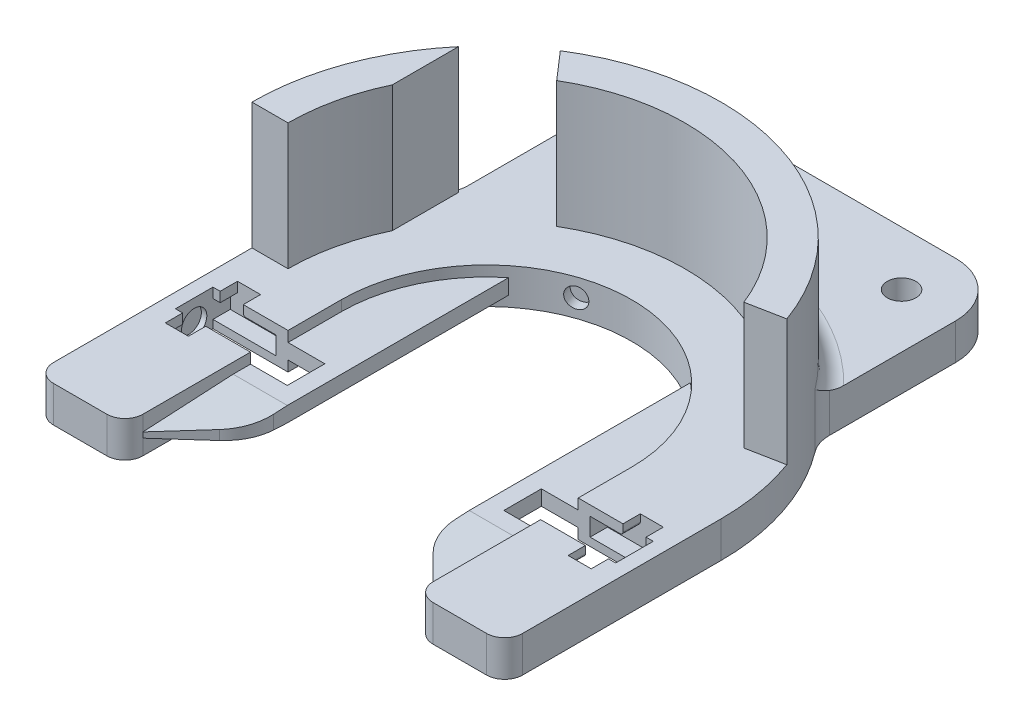
SolidWorks part; units mm, degrees
ref_plane "Front Plane" through (0, 0, 0) normal (0, 0, 1) x (1, 0, 0)
ref_plane "Top Plane" through (0, 0, 0) normal (0, 1, 0) x (1, 0, 0)
ref_plane "Right Plane" through (0, 0, 0) normal (1, 0, 0) x (0, 0, -1)
sketch "Sketch3" plane through (0, 0, 0) normal (0, 1, 0) x (1, 0, 0)
  line L0 (65, 0) -> (65, -55)
  line L1 (-65, 0) -> (65, 0) construction
  line L2 (60, -60) -> (45.2, -60)
  line L3 (40.2, -55) -> (40.2, 0)
  line L4 (25.2, -33.7868) -> (25.2, 31.3209)
  line L5 (29.5934, -44.3934) -> (40.2, -55)
  line L6 (54.9988, 0) -> (54.9988, -60)
  line L7 (0, -55) -> (0, 55) construction
  line L8 (-54.9988, 0) -> (-54.9988, -60)
  line L9 (-29.5934, -44.3934) -> (-40.2, -55)
  line L10 (-25.2, -33.7868) -> (-25.2, 31.3209)
  line L11 (-40.2, -55) -> (-40.2, 0)
  line L12 (-60, -60) -> (-45.2, -60)
  line L13 (-65, 0) -> (-65, -55)
  line L14 (-50, 80) -> (-50, 41.5331)
  line L15 (-35, 95) -> (35, 95)
  line L16 (50, 80) -> (50, 41.5331)
  arc A0 (65, 0) -> (-65, 0) centre (0, 0) ccw
  arc A1 (40.2, 0) -> (-40.2, 0) centre (0, 0) ccw
  arc A2 (60, -60) -> (65, -55) centre (60, -55) ccw
  arc A3 (45.2, -60) -> (40.2, -55) centre (45.2, -55) cw
  arc A4 (25.2, -33.7868) -> (29.5934, -44.3934) centre (40.2, -33.7868) ccw
  arc A5 (-54.9988, 0) -> (54.9988, 0) centre (0, 0) cw
  arc A6 (-25.2, -33.7868) -> (-29.5934, -44.3934) centre (-40.2, -33.7868) cw
  arc A7 (-45.2, -60) -> (-40.2, -55) centre (-45.2, -55) ccw
  arc A8 (-60, -60) -> (-65, -55) centre (-60, -55) cw
  arc A9 (50, 80) -> (35, 95) centre (35, 80) ccw
  arc A10 (-50, 80) -> (-35, 95) centre (-35, 80) cw
  circle A11 centre (-35, 80) radius 3.9688
  circle A12 centre (35, 80) radius 3.9688
  point P12 (65, -60)
  point P16 (40.2, -60)
  point P19 (25.2, -40)
  point P37 (-25.2, -40)
  point P38 (-40.2, -60)
  point P39 (-65, -60)
  point P45 (0, 65)
  point P52 (0, 95)
  dimension "130" = 130
  dimension "D4" = 80.4
  dimension "D8" = 5
  dimension "D9" = 15
  dimension "D10" = 54.9988
  dimension "D11" = 15
  dimension "D14" = 7.9375
  dimension "D2" = 60
  dimension "D3" = 24.8
  dimension "D5" = 15
  dimension "D6" = 5
  dimension "D7" = 15
  dimension "D12" = 30
  dimension "D13" = 100
extrude "Boss-Extrude1" add sketch "Sketch3" along normal mid plane 4.2 contours A1 L1 L10 | L1 L11 L9 A6 L10 | L4 L1 A1 | L1 L4 A4 L5 L3 region at (33.1426, 0, 23.8401) region at (31.3077, 0, -12.105) region at (-31.3077, 0, -12.105) region at (-33.1426, 0, 23.8401)
extrude "Boss-Extrude2" add sketch "Sketch3<3>" along normal mid plane 10 contours A5 L1 A1 | L1 L3 A3 L2 L6 | L1 L8 L12 A7 L11 region at (47.6376, 0, 29.8244) region at (47.5994, 0, -1.2298) region at (-47.6376, 0, 29.8244)
sketch "Sketch3<3>" plane through (0, 0, 0) normal (0, 1, 0) x (1, 0, 0) same geometry as "Sketch3"
extrude "Boss-Extrude3" add sketch "Sketch3<4>" against normal blind 5 and the other way blind 40 contours A0 L1 A5 | L1 L13 A8 L12 L8 | L1 L6 L2 A2 L0 region at (59.9643, 0, 29.7394) region at (59.9994, 0, -1.4534) region at (-59.9643, 0, 29.7394)
sketch "Sketch3<4>" plane through (0, 0, 0) normal (0, 1, 0) x (1, 0, 0) same geometry as "Sketch3"
sketch "Sketch4" plane through (0, 0, 0) normal (1, 0, 0) x (0, 0, -1)
  line L0 (-45, 5) -> (-60, 5)
  line L1 (-60, 5) -> (-60, 40)
  line L2 (-60, 40) -> (0, 40)
  line L3 (0, -5) -> (-55, -5) construction
  line L4 (0, 40) -> (-55, 40) construction
  line L5 (-60, 40) -> (-60, -5) construction
  arc A0 (-45, 5) -> (0, 40) centre (0, -6.4286) cw
  dimension "D2" = 15
  dimension "D1" = 10
extrude "Cut-Extrude1" cut sketch "Sketch4" against normal through all both and the other way through all
sketch "Sketch5" plane through (0, 40, 0) normal (0, 1, 0) x (1, 0, 0)
  line L0 (0, 0) -> (-42.6438, 49.0561) construction
  line L2 (-49.6832, 41.9115) -> (-43.0281, 34.2556) construction
  line L4 (-34.5891, 55.0327) -> (-27.9339, 47.3768)
  line L5 (0, 0) -> (0, 65) construction
  line L6 (-49.6832, 41.9115) -> (-49.6832, 23.5889)
  line L7 (0, 0) -> (63.8058, 12.4026) construction
  line L8 (51.1803, 20.1356) -> (61.1381, 22.0712)
  line L9 (54.9988, 0) -> (54.9988, -45)
  line L10 (54.9988, -45) -> (65, -45)
  line L11 (65, -45) -> (65, 0)
  line L12 (65, -45) -> (65, 0) construction
  line L13 (54.9988, 0) -> (54.9988, -45) construction
  line L14 (54.9988, -45) -> (65, -45) construction
  line L16 (-65, -45) -> (-54.9988, -45)
  line L17 (-65, -45) -> (-65, 0)
  line L18 (-65, 0) -> (-54.9988, 0)
  line L19 (-54.9988, -45) -> (-54.9988, 0)
  arc A0 (65, 0) -> (-65, 0) centre (0, 0) ccw construction
  arc A1 (-49.6832, 41.9115) -> (-34.5891, 55.0327) centre (0, 0) cw
  arc A2 (-43.0281, 34.2556) -> (-27.9339, 47.3768) centre (0, 0) cw
  arc A3 (54.9988, 0) -> (-54.9988, 0) centre (0, 0) ccw construction
  arc A4 (-49.6832, 23.5889) -> (-43.0281, 34.2556) centre (0, 0) cw
  arc A5 (54.9988, 0) -> (-54.9988, 0) centre (0, 0) ccw construction
  arc A6 (61.1381, 22.0712) -> (65, 0) centre (0, 0) cw
  arc A7 (51.1803, 20.1356) -> (54.9988, 0) centre (0, 0) cw
  dimension "D2" = 20
  dimension "D3" = 10
  dimension "D4" = 120
  dimension "D1" = 41
  dimension "D6" = 10
extrude "Cut-Extrude2" cut sketch "Sketch5" against normal blind 35
ref_axis "Axis1" through (0, 42.25, 0) along (0, -1, 0)
ref_plane "Plane1" through (0, 0, 0) normal (0.3256, 0, 0.9455) x (0, -1, 0)
sketch "Sketch6" plane through (0, 0, 0) normal (0.3256, 0, 0.9455) x (0, -1, 0)
  circle A0 centre (0, 0) radius 2.75
  dimension "D1" = 5.5
extrude "Cut-Extrude3" cut sketch "Sketch6" against normal blind 43
sketch "Sketch7" plane through (0, 5, 0) normal (0, 1, 0) x (1, 0, 0)
  line L0 (65, -55) -> (65, 0) construction
  line L1 (30, -14.8) -> (61, -14.8)
  line L2 (30, -14.8) -> (30, -25.2)
  line L3 (30, -25.2) -> (61, -25.2)
  line L4 (61, -14.8) -> (61, -25.2)
  line L6 (0, -24.75) -> (0, 24.75) construction
  line L7 (-61, -14.8) -> (-61, -25.2)
  line L8 (-30, -25.2) -> (-61, -25.2)
  line L9 (-30, -14.8) -> (-30, -25.2)
  line L10 (-30, -14.8) -> (-61, -14.8)
  line L11 (60, -60) -> (45.2, -60) construction
  point P7 (61, -20)
  dimension "D1" = 10.4
  dimension "D2" = 31
  dimension "D3" = 4
  dimension "D4" = 40
extrude "Cut-Extrude4" cut sketch "Sketch7" against normal through all
sketch "Sketch8" plane through (0, 0, 0) normal (0, 1, 0) x (1, 0, 0)
  line L0 (61, -25.2) -> (61, -14.8) construction
  line L1 (43.5, -10) -> (61, -10)
  line L2 (43.5, -10) -> (43.5, -30)
  line L3 (43.5, -30) -> (61, -30)
  line L4 (61, -10) -> (61, -30)
  line L6 (61, -14.8) -> (40.2, -14.8) construction
  line L7 (0, -24.75) -> (0, 24.75) construction
  line L8 (-61, -10) -> (-61, -30)
  line L9 (-43.5, -30) -> (-61, -30)
  line L10 (-43.5, -10) -> (-43.5, -30)
  line L11 (-43.5, -10) -> (-61, -10)
  dimension "D1" = 20
  dimension "D2" = 17.5
  dimension "D3" = 4.8
extrude "Cut-Extrude5" cut sketch "Sketch8" against normal blind 2.75 and the other way blind 2.25
sketch "Sketch12" plane through (61, 0, 0) normal (-1, 0, 0) x (0, 0, 1)
  line L0 (0, 0) -> (20, 0) construction
  circle A1 centre (20, -1) radius 3.5
  dimension "D1" = 20
  dimension "D2" = 7
  dimension "D3" = 1
extrude "Cut-Extrude7" cut sketch "Sketch12" against normal blind 1.5
sketch "Sketch13" plane through (-61, 0, 0) normal (1, 0, 0) x (0, 0, -1)
  line L0 (0, 0) -> (-20, 0) construction
  circle A0 centre (-20, -1) radius 3.5
  dimension "D1" = 7
  dimension "D2" = 20
  dimension "D3" = 1
extrude "Cut-Extrude8" cut sketch "Sketch13" against normal blind 1.5
sketch "Sketch14" plane through (0, 5, 0) normal (0, 1, 0) x (1, 0, 0)
  line L0 (-61, -14.8) -> (-61, -25.2) construction
  line L1 (-59, -10) -> (-52.6, -10)
  line L2 (-59, -10) -> (-59, -14.8)
  line L3 (-59, -14.8) -> (-52.6, -14.8)
  line L4 (-52.6, -10) -> (-52.6, -14.8)
  line L5 (-40.2, -14.8) -> (-61, -14.8) construction
  line L6 (-59, -25.2) -> (-52.6, -25.2)
  line L7 (-59, -25.2) -> (-59, -30)
  line L8 (-59, -30) -> (-52.6, -30)
  line L9 (-52.6, -25.2) -> (-52.6, -30)
  line L10 (-61, -25.2) -> (-40.2, -25.2) construction
  line L11 (0, -24.75) -> (0, 24.75) construction
  line L12 (52.6, -25.2) -> (52.6, -30)
  line L13 (59, -30) -> (52.6, -30)
  line L14 (59, -25.2) -> (59, -30)
  line L15 (59, -25.2) -> (52.6, -25.2)
  line L16 (52.6, -10) -> (52.6, -14.8)
  line L17 (59, -14.8) -> (52.6, -14.8)
  line L18 (59, -10) -> (59, -14.8)
  line L19 (59, -10) -> (52.6, -10)
  line L20 (-52.6, -10) -> (-52.6, -30) construction
  point P24 (-52.6, -20)
  dimension "D1" = 20
  dimension "D2" = 6.4
  dimension "D3" = 2
  dimension "D4" = 5.2
  dimension "D6" = 2
extrude "Cut-Extrude9" cut sketch "Sketch14" against normal up to next
fillet "Fillet2" radius 0.75 4 edges at (52.6, 2.25, 27.6) (52.6, 2.25, 12.4) (-52.6, 2.25, 27.6) (-52.6, 2.25, 12.4)
sketch "Sketch15" plane through (0, 5, 0) normal (0, 1, 0) x (1, 0, 0)
  line L0 (0, 0) -> (0, 40.2) construction
  line L1 (0, 0) -> (-13.0878, 38.0098) construction
  line L7 (-17.6258, 41.2066) -> (-11.48, 43.3228)
  line L8 (-17.6258, 41.2066) -> (-16.4863, 37.8973)
  line L9 (-16.4863, 37.8973) -> (-10.3405, 40.0135)
  line L10 (-11.48, 43.3228) -> (-10.3405, 40.0135)
  arc A0 (40.2, 0) -> (-40.2, 0) centre (0, 0) ccw construction
  point P12 (-13.4134, 38.9554)
  dimension "D1" = 19
  dimension "D2" = 3.5
  dimension "D3" = 6.5
  dimension "D4" = 1
extrude "Cut-Extrude10" [suppressed] cut sketch "Sketch15" against normal blind 8.5
sketch "Sketch16" [suppressed] plane through (-14.5529, 0, -42.2647) normal (0.3256, 0, 0.9455) x (0.9455, 0, -0.3256)
  line L0 (-3.25, 0) -> (-3.25, -3.24)
  line L1 (-3.25, -3.24) -> (3.25, -3.24)
  line L2 (3.25, -3.24) -> (3.25, 0)
  arc A0 (-3.25, 0) -> (3.25, 0) centre (0, 0) ccw
  point P1 (0, -3.25)
  line M5 (-3.25, 5) -> (-3.25, -3.5)
  line M6 (-3.25, -3.5) -> (3.25, -3.5)
  line M7 (3.25, -3.5) -> (3.25, 5)
  dimension "D1" = 6.5
  dimension "D2" = 0.01
extrude "Boss-Extrude4" [suppressed] add sketch "Sketch16" along normal blind 3.5 contours A0 M5 M6 | A0 L1 M7 | A0 L1 M5
extrude "Boss-Extrude7" add sketch "Sketch3<5>" along normal mid plane 10 contours A10 L14 A0 L16 A9 L15 A11 A12 region at (0, 0, -75.2597)
sketch "Sketch3<5>" plane through (0, 0, 0) normal (0, 1, 0) x (1, 0, 0) same geometry as "Sketch3"
fillet "Fillet4" radius 10 2 edges at (-50, 0, -41.5331) (50, 0, -41.5331)
fillet "Fillet6" radius 5 1 edges at (11.8341, 5, -63.9136)
sketch "Sketch18" plane through (0, 0, 0) normal (1, 0, 0) x (0, 0, -1)
  line L0 (-55, 2.1) -> (-55, -2.1) construction
  line L1 (-55, 0.75) -> (-30, 2.1)
  line L2 (-55, 0.75) -> (-55, -0.75) construction
  line L3 (-55, -0.75) -> (-30, -2.1)
  line L4 (-30, 2.1) -> (-30, -2.1) construction
  line L5 (-30, 2.1) -> (-55, 2.1)
  line L6 (-55, 2.1) -> (-55, 0.75)
  line L7 (-55, -0.75) -> (-55, -2.1)
  line L8 (-55, -2.1) -> (-30, -2.1)
  point P4 (-30, 0)
  point P5 (-55, 0)
  dimension "D1" = 4.2
  dimension "D2" = 1.5
  dimension "D3" = 25
extrude "Cut-Extrude11" cut sketch "Sketch18" against normal mid plane 80.4
equation "\"D3@Sketch8\"=(\"D1@Sketch8\"-\"D1@Sketch7\")/2"
